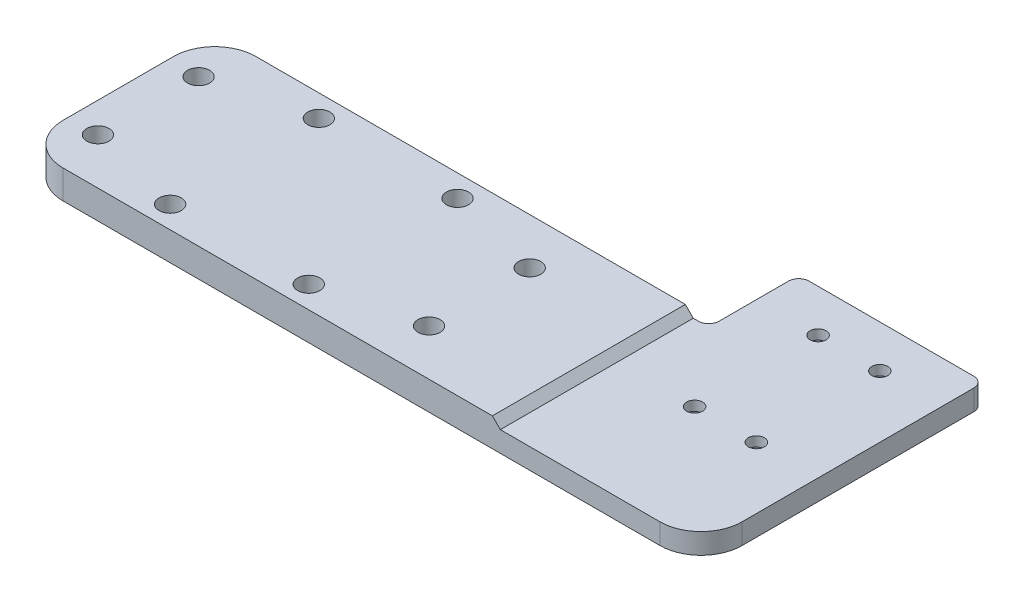
SolidWorks part; units mm, degrees
ref_plane "Front Plane" through (0, 0, 0) normal (0, 0, 1) x (1, 0, 0)
ref_plane "Top Plane" through (0, 0, 0) normal (0, 1, 0) x (1, 0, 0)
ref_plane "Right Plane" through (0, 0, 0) normal (1, 0, 0) x (0, 0, -1)
sketch "Sketch1" plane through (0, 0, 0) normal (0, 1, 0) x (1, 0, 0)
  line L6 (-38, -18.75) -> (94, -18.75)
  line L9 (-38, -18.75) -> (-38, 18.75)
  line L10 (-38, 18.75) -> (58, 18.75)
  line L11 (94, -18.75) -> (94, 36.25)
  line L12 (0, 0) -> (-38, 0) construction
  line L13 (0, 0) -> (0, 18.75) construction
  line L15 (58, 18.75) -> (58, 36.25)
  line L16 (58, 36.25) -> (94, 36.25)
  point P0 (0, 0)
  dimension "D1" = 37.5
  dimension "D2" = 38
  dimension "D3" = 58
  dimension "D4" = 17.5
  dimension "D5" = 36
extrude "Boss-Extrude1" add sketch "Sketch1" along normal blind 5.55
sketch "Sketch2" plane through (0, 5.55, 0) normal (0, 1, 0) x (1, 0, 0)
  line L0 (94, 36.25) -> (58, 36.25) construction
  line L1 (55, 36.25) -> (94, 36.25)
  line L2 (55, 36.25) -> (55, -18.75)
  line L3 (55, -18.75) -> (94, -18.75)
  line L4 (94, 36.25) -> (94, -18.75)
  line L5 (58, 36.25) -> (58, 18.75) construction
  dimension "D1" = 3
extrude "Cut-Extrude1" cut sketch "Sketch2" against normal blind 1.55
fillet "Fillet1" radius 8 3 edges at (94, 2, 18.75) (-38, 2.775, 18.75) (-38, 2.775, -18.75)
hole_wizard "CBORE for M2.5 Pan Head Machine Screw1" positions "Sketch3" profile "Sketch4" counterbore size "M2.5" standard "ANSI Metric" end condition through all
sketch "Sketch3" plane through (0, 0, 0) normal (0, -1, 0) x (-1, 0, 0)
  arc A0 (-83.05, 28) -> (-80.95, 28) centre (-82, 28) ccw construction
  arc A1 (-83.05, 4) -> (-80.95, 4) centre (-82, 4) ccw construction
  arc A2 (-71.05, 4) -> (-68.95, 4) centre (-70, 4) ccw construction
  arc A3 (-68.95, 28) -> (-71.05, 28) centre (-70, 28) ccw construction
  point P0 (-82, 28)
  point P2 (-82, 4)
  point P4 (-70, 4)
  point P6 (-70, 28)
sketch "Sketch4" plane through (82, 0, -28) normal (1, 0, 0) x (0, 0, -1)
  line L0 (0, 0) -> (0, 5.55)
  line L1 (0, 5.55) -> (1.55, 5.55)
  line L3 (1.55, 5.55) -> (1.55, 2.1)
  line L4 (1.55, 2.1) -> (3, 2.1)
  line L5 (3, 2.1) -> (3, 0)
  line L7 (3, 0) -> (0, 0)
  line L11 (0, -6.35) -> (0, 107.95) construction
  dimension "Thru Hole Dia." = 3.1
  dimension "Thru Hole Depth" = 5.55
  dimension "C'Bore Dia." = 6
  dimension "C'Bore Depth" = 2.1
fillet "Fillet2" radius 2 3 edges at (58, 2, -18.75) (58, 2, -36.25) (94, 2, -36.25)
chamfer "Chamfer1" distance 1.55 angle 45 1 edges at (55, 5.55, 0)
hole_wizard "#6 Clearance Hole1" positions "Sketch5" profile "Sketch6" hole size "#6" standard "ANSI Inch" end condition through all
sketch "Sketch5" plane through (0, 0, 0) normal (0, -1, 0) x (-1, 0, 0)
  line L1 (-32.1752, -9.779) -> (32.1752, -9.779) construction
  line L2 (-32.1752, -9.779) -> (-32.1752, 9.779) construction
  line L3 (-32.1752, 9.779) -> (32.1752, 9.779) construction
  line L4 (32.1752, -9.779) -> (32.1752, 9.779) construction
  line L5 (-32.1752, -9.779) -> (32.1752, 9.779) construction
  line L6 (-32.1752, 9.779) -> (32.1752, -9.779) construction
  arc A1 (-32.9371, -8.2007) -> (-32.1752, -11.5316) centre (-32.1752, -9.779) ccw construction
  arc A2 (-12.1178, 14.45) -> (-14.8229, 14.45) centre (-13.4704, 14.45) ccw construction
  arc A3 (14.8229, 14.45) -> (12.1178, 14.45) centre (13.4704, 14.45) ccw construction
  arc A4 (-14.8229, -14.45) -> (-12.1178, -14.45) centre (-13.4704, -14.45) ccw construction
  arc A5 (12.1178, -14.45) -> (14.8229, -14.45) centre (13.4704, -14.45) ccw construction
  point P0 (-32.1752, 9.779)
  point P2 (-32.1752, -9.779)
  point P4 (32.1752, 9.779)
  point P6 (32.1752, -9.779)
  point P88 (13.4704, -14.45)
  point P90 (-13.4704, -14.45)
  point P92 (13.4704, 14.45)
  point P94 (-13.4704, 14.45)
sketch "Sketch6" plane through (32.1752, 0, -9.779) normal (1, 0, 0) x (0, 0, -1)
  line L0 (0, 0) -> (0, 5.55)
  line L1 (0, 5.55) -> (2.1526, 5.55)
  line L2 (2.1526, 5.55) -> (2.1526, 0)
  line L5 (2.1526, 0) -> (0, 0)
  line L11 (0, -6.35) -> (0, 107.95) construction
  dimension "Thru Hole Dia." = 4.3053
  dimension "Thru Hole Depth" = 5.55
